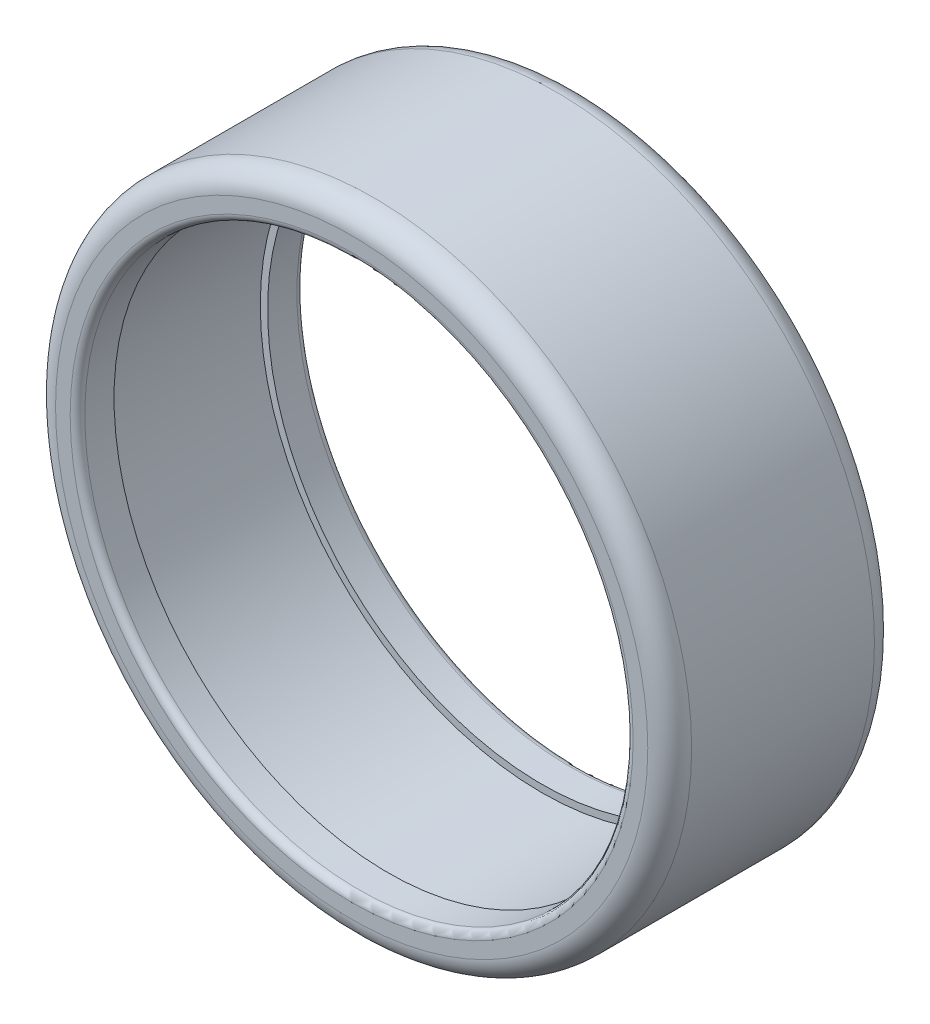
SolidWorks part; units mm, degrees
ref_plane "Front Plane" through (0, 0, 0) normal (0, 0, 1) x (1, 0, 0)
ref_plane "Top Plane" through (0, 0, 0) normal (0, 1, 0) x (1, 0, 0)
ref_plane "Right Plane" through (0, 0, 0) normal (1, 0, 0) x (0, 0, -1)
sketch "Sketch1" plane through (0, 0, 0) normal (0, 0, 1) x (1, 0, 0)
  circle A0 centre (0, 0) radius 37.5
  dimension "D1" = 75
extrude "Extrude-Thin3" add sketch "Sketch1" along normal blind 31 thin contours A0 thin type one direction wall 6
fillet "Fillet5" radius 3 2 edges at (43.5, 0, 0) (43.5, 0, 31)
fillet "Fillet6" radius 1 2 edges at (37.5, 0, 0) (37.5, 0, 31)
shell "Shell4" thickness 5 removed face at (37.5, 0, 1)
